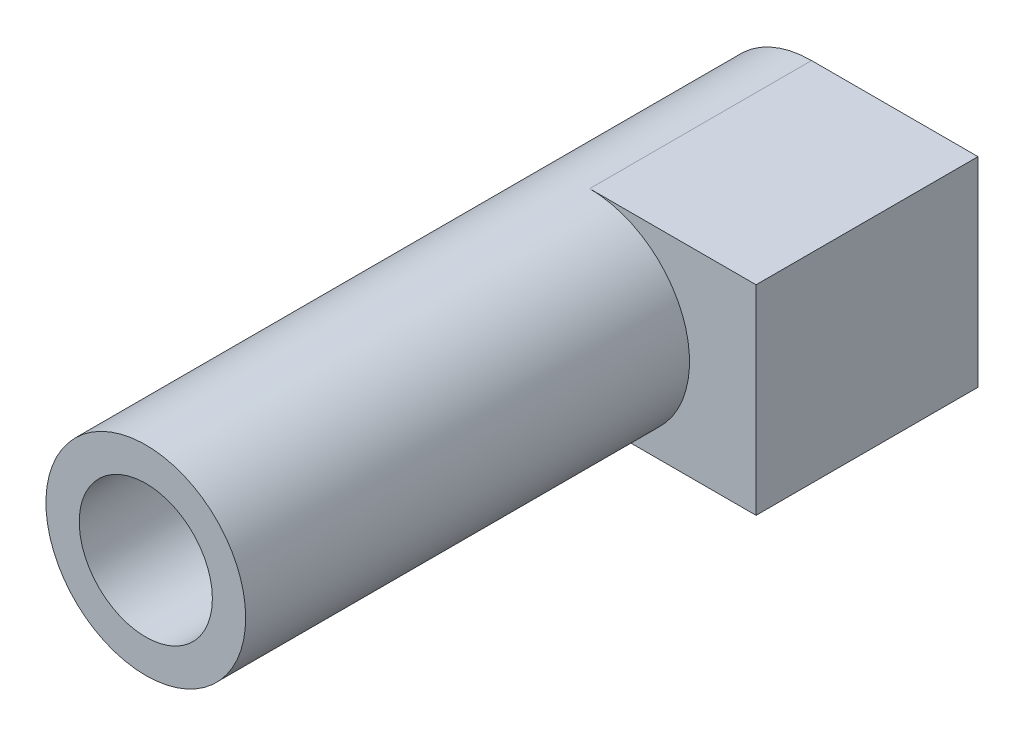
SolidWorks part; units mm, degrees
ref_plane "Front" through (0, 0, 0) normal (0, 0, 1) x (1, 0, 0)
ref_plane "Top" through (0, 0, 0) normal (0, 1, 0) x (1, 0, 0)
ref_plane "Right" through (0, 0, 0) normal (1, 0, 0) x (0, 0, -1)
sketch "Esquisse1" plane through (0, 0, 0) normal (0, 0, 1) x (1, 0, 0)
  line L0 (0, 9) -> (15, 9)
  line L1 (15, 9) -> (15, -9)
  line L2 (15, -9) -> (0, -9)
  circle A0 centre (0, 0) radius 6
  circle A1 centre (0, 0) radius 9
  dimension "D1" = 12
  dimension "D3" = 15
  dimension "D2" = 3
extrude "Boss.-Extru.1" add sketch "Esquisse1" along normal blind 20 contours A1 L2 L1 L0 | A1 A0 region at (10.7799, 0, 0) region at (6.184, 6.184, 0)
extrude "Boss.-Extru.2" add sketch "Esquisse1<3>" along normal blind 60 contours A1 A0 region at (6.184, 6.184, 0)
sketch "Esquisse1<3>" plane through (0, 0, 0) normal (0, 0, 1) x (1, 0, 0) same geometry as "Esquisse1"
